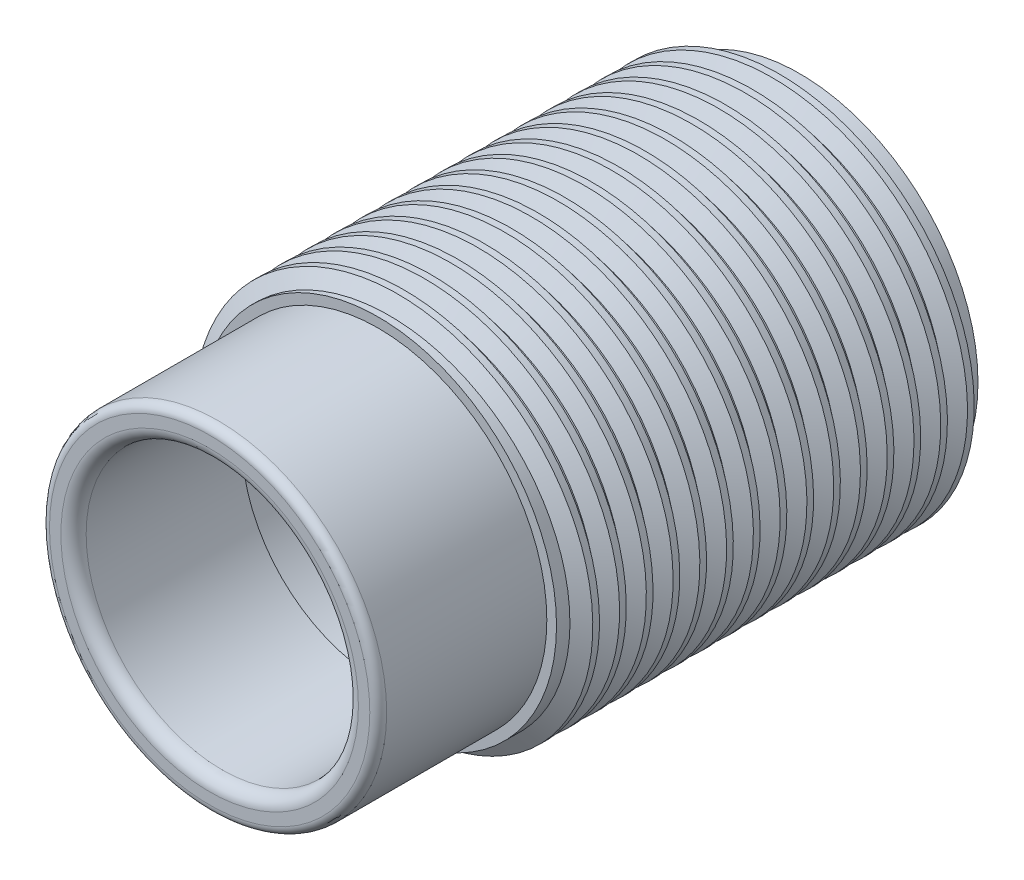
SolidWorks part; units mm, degrees
ref_plane "Plano frontal" through (0, 0, 0) normal (0, 0, 1) x (1, 0, 0)
ref_plane "Plano superior" through (0, 0, 0) normal (0, 1, 0) x (1, 0, 0)
ref_plane "Plano direito" through (0, 0, 0) normal (1, 0, 0) x (0, 0, -1)
ref_plane "Plano1" through (0, 0, 0) normal (0, -1, 0) x (1, 0, 0)
sketch "Esboço1" plane through (0, 0, 0) normal (0, -1, 0) x (1, 0, 0)
  line L0 (14.6396, -32.7347) -> (18.6396, -32.7347)
  line L1 (18.6396, -32.7347) -> (18.6396, 17.2653)
  line L2 (18.6396, 17.2653) -> (17.4896, 17.2653)
  line L3 (17.4896, 17.2653) -> (17.4896, 37.2653)
  line L4 (17.4896, 37.2653) -> (13.6396, 37.2653)
  line L5 (13.6396, 37.2653) -> (13.6396, 17.2653)
  line L6 (13.6396, 17.2653) -> (14.6396, 17.2653)
  line L7 (14.6396, 17.2653) -> (14.6396, -32.7347)
  line L8 (-2.5104, 69.0612) -> (-2.5104, 0) construction
  dimension "D1" = 21.15
  dimension "D2" = 20
  dimension "D3" = 16.15
  dimension "D4" = 1
  dimension "D5" = 50
  dimension "D6" = 20
revolve "Revolução1" add sketch "Esboço1" angle 360 about L8 reverse direction yes
thread "Rosca1" pitch 3.175 method extrude profile "Perfil da rosca1" start angle 0, offset 0, length 47, pitch 3.175, diameter 42.3
ref_plane "Plano2" through (-23.6604, 0, 17.2653) normal (0, 1, 0) x (1, 0, 0)
sketch "Perfil da rosca1" plane through (-23.6604, 0, 17.2653) normal (0, 1, 0) x (1, 0, 0)
  line L0 (0, 0) -> (0, 3.175) construction
  line L11 (0, 0) -> (0, 2.7781)
  line L12 (0, 2.7781) -> (-1.7185, 1.7859)
  line L13 (-1.7185, 1.7859) -> (-1.7185, 0.9922)
  line L15 (-1.7185, 0.9922) -> (0, 0)
  line L17 (-1.7185, 1.3891) -> (0, 1.3891) construction
  point P2 (0, 0)
  dimension "Pitch" = 3.175
  dimension "Profile_Angle" = 60
  dimension "Profile_Land" = 0.7937
  dimension "Profile_Height" = 1.7185
fillet "Fillet1" radius 1.5 1 edges at (-18.6604, 0, 37.2653)
fillet "Fillet2" radius 1 1 edges at (-22.5104, 0, 37.2653)
